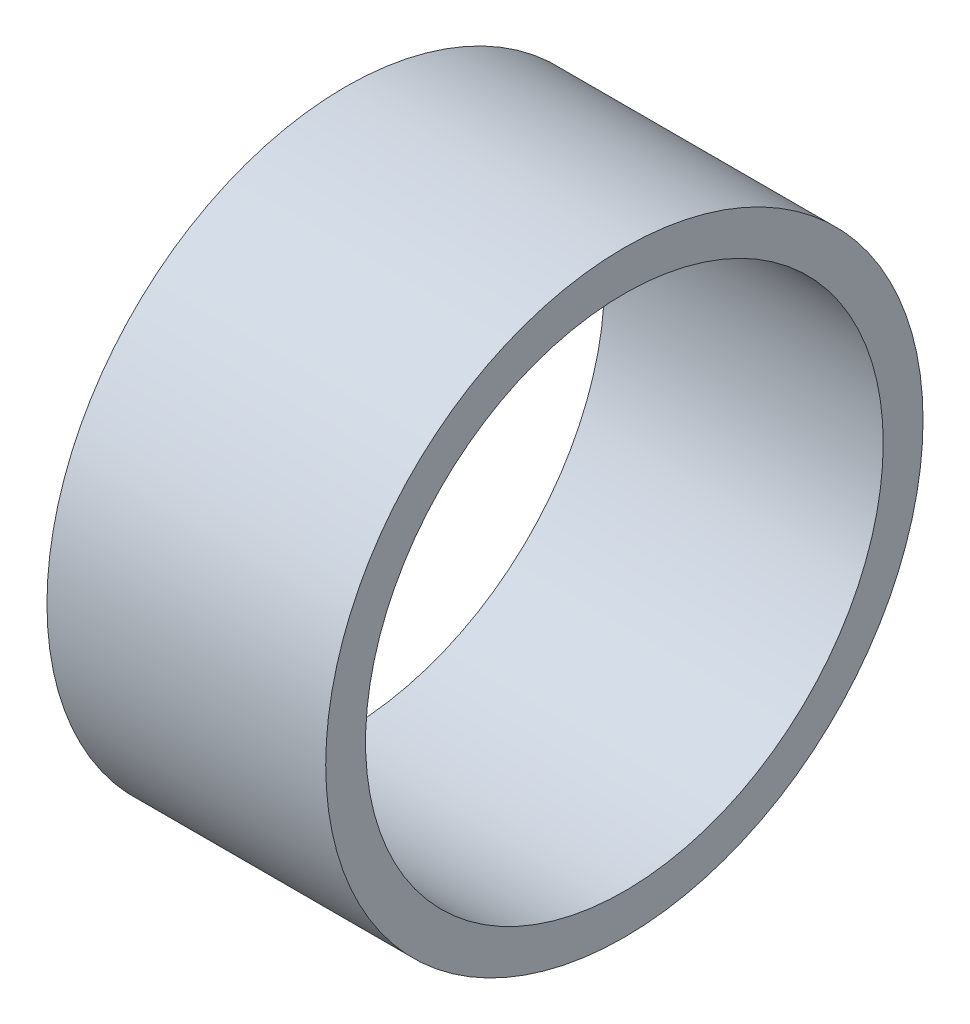
SolidWorks part; units mm, degrees
material "AISI 1020"
ref_plane "Front Plane" through (0, 0, 0) normal (0, 0, 1) x (1, 0, 0)
ref_plane "Top Plane" through (0, 0, 0) normal (0, 1, 0) x (1, 0, 0)
ref_plane "Right Plane" through (0, 0, 0) normal (1, 0, 0) x (0, 0, -1)
sketch "Sketch1" plane through (0, 0, 0) normal (1, 0, 0) x (0, 0, -1)
  circle A0 centre (0, 0) radius 23.8125
  circle A1 centre (0, 0) radius 20.6375
  dimension "D1" = 47.625
  dimension "D2" = 3.175
extrude "Boss-Extrude1" add sketch "Sketch1" along normal mid plane 22.225
ref_plane "Plane1" through (0, -23.8125, 0) normal (0, -1, 0) x (-1, 0, 0)
ref_plane "Plane2" through (0, 0, -23.8125) normal (0, 0, -1) x (-1, 0, 0)
